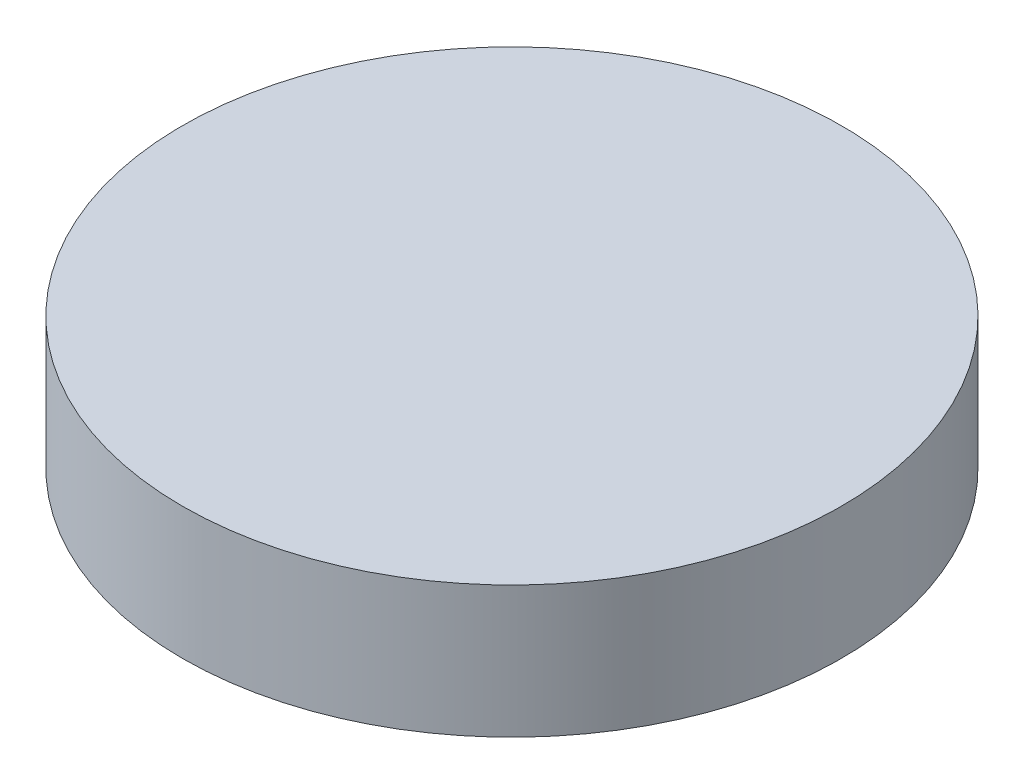
SolidWorks part; units mm, degrees
ref_plane "Front Plane" through (0, 0, 0) normal (0, 0, 1) x (1, 0, 0)
ref_plane "Top Plane" through (0, 0, 0) normal (0, 1, 0) x (1, 0, 0)
ref_plane "Right Plane" through (0, 0, 0) normal (1, 0, 0) x (0, 0, -1)
sketch "Sketch1" plane through (0, 0, 0) normal (0, 1, 0) x (1, 0, 0)
  circle A0 centre (0, 0) radius 3.175
  dimension "D1" = 6.35
extrude "Boss-Extrude1" add sketch "Sketch1" along normal blind 1.27
ref_axis "Axis1" through (0, 1.27, 0) along (0, -1, 0)
